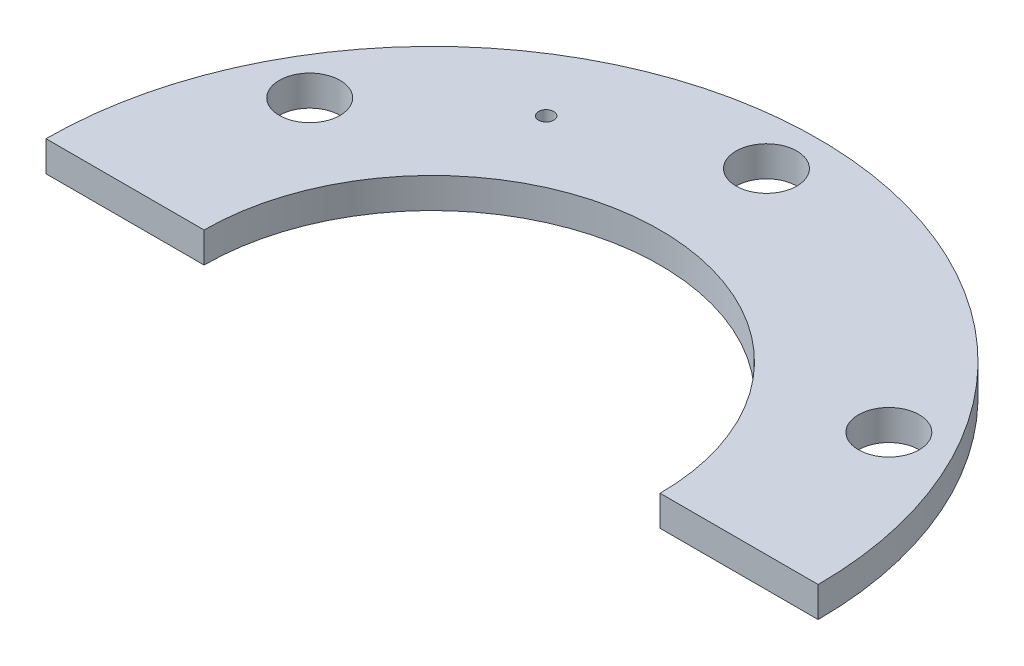
SolidWorks part; units mm, degrees
material "ABS"
ref_plane "Front Plane" through (0, 0, 0) normal (0, 0, 1) x (1, 0, 0)
ref_plane "Top Plane" through (0, 0, 0) normal (0, 1, 0) x (1, 0, 0)
ref_plane "Right Plane" through (0, 0, 0) normal (1, 0, 0) x (0, 0, -1)
sketch "Sketch1" plane through (0, 0, 0) normal (0, 1, 0) x (1, 0, 0)
  circle A0 centre (0, 0) radius 12.7
  dimension "D1" = 25.4
extrude "Boss-Extrude1" add sketch "Sketch1" along normal blind 1
sketch "Sketch19" plane through (0, 1, 0) normal (0, 1, 0) x (1, 0, 0)
  circle A0 centre (0, 11) radius 1
  circle A1 centre (9.5263, 5.5) radius 1
  circle A2 centre (9.5263, -5.5) radius 1
  circle A3 centre (0, -11) radius 1
  circle A4 centre (-9.5263, -5.5) radius 1
  circle A5 centre (-9.5263, 5.5) radius 1
  point P13 (0, 0)
  dimension "D1" = 2
  dimension "D2" = 11
  dimension "D3" = 6
extrude "Cut-Extrude1" cut sketch "Sketch19" against normal through all both and the other way through all
sketch "Sketch20" plane through (0, 1, 0) normal (0, 1, 0) x (1, 0, 0)
  circle A0 centre (0, 0) radius 7.5
  dimension "D1" = 15
extrude "Cut-Extrude2" cut sketch "Sketch20" against normal through all both and the other way through all
sketch "Sketch21" plane through (0, 0, 0) normal (0, 0, 1) x (1, 0, 0)
  line L1 (-36.7533, 32.3113) -> (29.1209, 32.3113)
  line L2 (-36.7533, 32.3113) -> (-36.7533, -19.668)
  line L3 (-36.7533, -19.668) -> (29.1209, -19.668)
  line L4 (29.1209, 32.3113) -> (29.1209, -19.668)
extrude "Cut-Extrude3" cut sketch "Sketch21" along normal through all
sketch "Sketch22" plane through (0, 1, 0) normal (0, 1, 0) x (1, 0, 0)
  line L0 (-9.5263, 5.5) -> (0, 11)
  line L1 (0, 0) -> (-5.125, 8.8768) construction
  circle A0 centre (-5.125, 8.8768) radius 0.25
  dimension "D1" = 0.5
  dimension "D2" = 10.25
extrude "Cut-Extrude4" cut sketch "Sketch22" against normal through all both and the other way through all contours L0 A0 | A0 L1 L0 | L1 A0 L0 region at (-5.125, 1, -8.8768)
